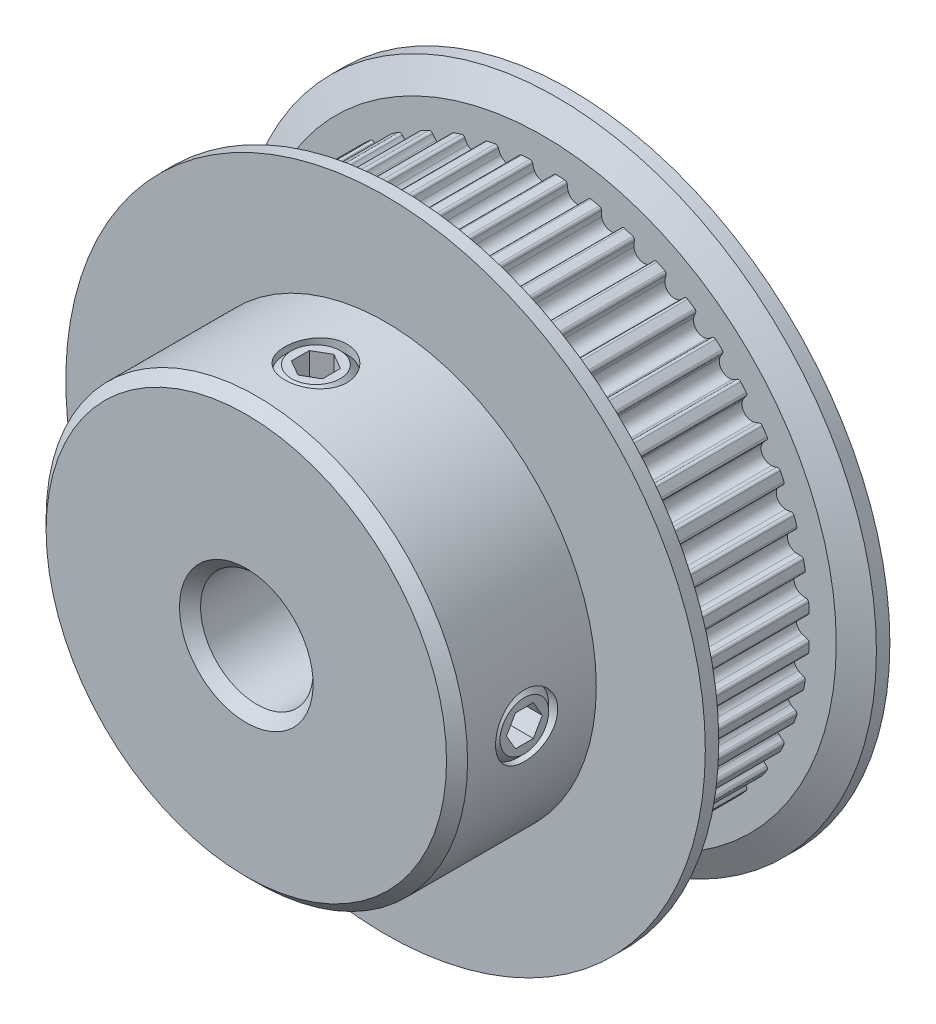
SolidWorks part; units mm, degrees
ref_plane "Front Plane" through (0, 0, 0) normal (0, 0, 1) x (1, 0, 0)
ref_plane "Top Plane" through (0, 0, 0) normal (0, 1, 0) x (1, 0, 0)
ref_plane "Right Plane" through (0, 0, 0) normal (1, 0, 0) x (0, 0, -1)
sketch "Sketch1" plane through (0, 0, 0) normal (0, 0, 1) x (1, 0, 0)
  line L1 (-1.8807, 14.274) -> (1.8807, 14.274) construction
  line L4 (0, 0) -> (0, 14.274) construction
  line L5 (0, 14.274) -> (0, 16.8906) construction
  line L6 (0, 15.278) -> (1.9957, 15.1471) construction
  line L7 (1.9957, 15.1471) -> (2.8688, 15.0321) construction
  line L8 (1.9957, 15.1471) -> (1.8807, 14.274) construction
  line L9 (-1.9957, 15.1471) -> (-1.8807, 14.274) construction
  line L10 (-1.9625, 14.8953) -> (-2.3761, 18.034)
  line L11 (-2.3761, 18.034) -> (2.3761, 18.034)
  line L12 (2.3761, 18.034) -> (1.9625, 14.8953)
  circle A0 centre (0, 0) radius 15.278 construction
  circle A1 centre (0, 0) radius 18.034 construction
  circle A2 centre (0, 0) radius 15.024 construction
  arc A3 (-0.4989, 14.5858) -> (0.4989, 14.5858) centre (0, 14.829) ccw
  arc A4 (-0.4989, 14.5858) -> (-0.5892, 14.8777) centre (0.4, 15.024) cw
  arc A5 (-1.9625, 14.8953) -> (-0.7451, 15.0055) centre (0, 0) cw
  arc A6 (-0.5892, 14.8777) -> (-0.7451, 15.0055) centre (-0.7376, 14.8557) ccw
  arc A7 (1.9625, 14.8953) -> (0.7451, 15.0055) centre (0, 0) ccw
  arc A8 (0.5892, 14.8777) -> (0.7451, 15.0055) centre (0.7376, 14.8557) cw
  arc A9 (0.4989, 14.5858) -> (0.5892, 14.8777) centre (-0.4, 15.024) ccw
  point P6 (0, 20.9083)
  point P11 (0, 15.278)
  point P13 (0, 18.034)
  point P14 (0, 15.024)
  dimension "D1" = 4.0177
  dimension "D2" = 1.6126
sketch "Sketch2" plane through (0, 0, 0) normal (1, 0, 0) x (0, 0, -1)
  line L0 (-9.1313, 3.175) -> (9.1313, 3.175)
  line L1 (-9.1313, 3.175) -> (-9.1313, 11.885)
  line L2 (-9.1313, 11.885) -> (-1.2787, 11.885)
  line L3 (-1.2787, 11.885) -> (-1.2787, 18.034)
  line L4 (-1.2787, 18.034) -> (0.2413, 18.034) construction
  line L5 (0.2413, 18.034) -> (0.2413, 15.024) construction
  line L6 (0.2413, 15.024) -> (7.6113, 15.024)
  line L7 (7.6113, 15.024) -> (7.6113, 18.034) construction
  line L8 (7.6113, 18.034) -> (9.1313, 18.034) construction
  line L9 (9.1313, 18.034) -> (9.1313, 3.175)
  line L10 (-9.1313, 0) -> (9.1313, 0) construction
  line L11 (8.3713, 18.034) -> (7.6113, 16.529)
  line L12 (0.2413, 16.529) -> (-0.5187, 18.034)
  line L13 (-1.2787, 18.034) -> (-0.5187, 18.034)
  line L14 (0.2413, 16.529) -> (0.2413, 15.024)
  line L15 (7.6113, 15.024) -> (7.6113, 16.529)
  line L16 (8.3713, 18.034) -> (9.1313, 18.034)
  arc A0 (0.2413, 16.529) -> (-0.5187, 18.034) centre (-1.6288, 16.529) ccw construction
  arc A1 (7.6113, 16.529) -> (8.3713, 18.034) centre (9.4814, 16.529) cw construction
  point P12 (0.2413, 16.529)
  point P14 (-0.5187, 18.034)
  point P20 (7.6113, 16.529)
  point P21 (8.3713, 18.034)
  point P25 (7.6113, 0)
  point P26 (0.2413, 0)
revolve "Revolve1" add sketch "Sketch2" angle 360 mid plane about L10
sketch "Sketch3" plane through (0, 0, 0) normal (0, 0, 1) x (1, 0, 0)
  line L6 (2.3761, 18.034) -> (-2.3761, 18.034)
  line L7 (1.9625, 14.8953) -> (2.3761, 18.034)
  line L8 (-2.3761, 18.034) -> (-1.9625, 14.8953)
  line L9 (2.3761, 18.034) -> (-2.3761, 18.034)
  line L10 (1.9625, 14.8953) -> (2.3761, 18.034)
  line L11 (-2.3761, 18.034) -> (-1.9625, 14.8953)
  arc A8 (1.9625, 14.8953) -> (0.7451, 15.0055) centre (0, 0) ccw
  arc A9 (0.7451, 15.0055) -> (0.5892, 14.8777) centre (0.7376, 14.8557) ccw
  arc A10 (0.4989, 14.5858) -> (0.5892, 14.8777) centre (-0.4, 15.024) ccw
  arc A11 (-0.4989, 14.5858) -> (0.4989, 14.5858) centre (0, 14.829) ccw
  arc A12 (-0.5892, 14.8777) -> (-0.4989, 14.5858) centre (0.4, 15.024) ccw
  arc A13 (-0.5892, 14.8777) -> (-0.7451, 15.0055) centre (-0.7376, 14.8557) ccw
  arc A14 (-0.7451, 15.0055) -> (-1.9625, 14.8953) centre (0, 0) ccw
  arc A15 (1.9625, 14.8953) -> (0.7451, 15.0055) centre (0, 0) ccw
  arc A16 (0.7451, 15.0055) -> (0.5892, 14.8777) centre (0.7376, 14.8557) ccw
  arc A17 (0.4989, 14.5858) -> (0.5892, 14.8777) centre (-0.4, 15.024) ccw
  arc A18 (-0.4989, 14.5858) -> (0.4989, 14.5858) centre (0, 14.829) ccw
  arc A19 (-0.5892, 14.8777) -> (-0.4989, 14.5858) centre (0.4, 15.024) ccw
  arc A20 (-0.5892, 14.8777) -> (-0.7451, 15.0055) centre (-0.7376, 14.8557) ccw
  arc A21 (-0.7451, 15.0055) -> (-1.9625, 14.8953) centre (0, 0) ccw
  dimension "D1" = 0
extrude "Cut-Extrude1" cut sketch "Sketch3" against normal up to vertex (7.6113 mm away) from vertex up to point (0, 15.024, -7.6113) starting at point (0, 15.024, -0.2413)
pattern_circular "CirPattern1" count 48 over 360 about axis through (0, 0, 9.1313) along (0, 0, 1) of "Cut-Extrude1"
sketch "Sketch4" plane through (0, 0, 0) normal (1, 0, 0) x (0, -1, 0)
  line L0 (0, -1.2787) -> (0, -9.1313) construction
  line L1 (-11.885, -1.2787) -> (11.885, -1.2787) construction
  line L2 (-11.885, -9.1313) -> (11.885, -9.1313) construction
  circle A0 centre (0, -5.205) radius 1.7526
extrude "Cut-Extrude2" cut sketch "Sketch4" along normal through all
ref_plane "Plane1" through (0, 0, 5.205) normal (0, 0, 1) x (1, 0, 0)
sketch "Sketch5" plane through (0, 0, 5.205) normal (0, 0, 1) x (1, 0, 0)
  line L0 (0, 0.1664) -> (0, 11.885) construction
  line L1 (3.175, -1.3716) -> (3.175, 0)
  line L2 (3.556, -1.7526) -> (11.3741, -1.7526)
  line L3 (3.175, 0) -> (11.885, 0) construction
  line L4 (3.175, 0) -> (11.7551, 0)
  line L5 (11.7551, 0) -> (11.7551, -1.3716)
  line L6 (3.556, -1.7526) -> (3.175, -1.3716)
  line L7 (11.7551, -1.3716) -> (11.3741, -1.7526)
  circle A0 centre (0, 0) radius 11.885 construction
  circle A1 centre (0, 0) radius 3.175 construction
  point P2 (3.175, -1.7526)
  point P11 (11.7551, -1.7526)
revolve "Revolve2" add sketch "Sketch5" angle 360 mid plane about L4
sketch "Sketch6" plane through (11.7551, 5.3841, 0) normal (-1, 0, 0) x (0, -1, 0)
  line L1 (5.3841, 6.2169) -> (4.5078, 5.7109)
  line L2 (4.5078, 5.7109) -> (4.5078, 4.6991)
  line L3 (4.5078, 4.6991) -> (5.3841, 4.1931)
  line L4 (5.3841, 4.1931) -> (6.2604, 4.6991)
  line L5 (6.2604, 4.6991) -> (6.2604, 5.7109)
  line L6 (6.2604, 5.7109) -> (5.3841, 6.2169)
  circle A0 centre (5.3841, 5.205) radius 0.8763 construction
  dimension "D1" = 1.7526
extrude "Cut-Extrude3" cut sketch "Sketch6" along normal blind 1.3144
pattern_circular "CirPattern2" count 2 over 90 about axis through (0, 0, 9.1313) along (0, 0, 1) of "Cut-Extrude2", "Revolve2", "Cut-Extrude3"
chamfer "Chamfer1" distance 0.5943 angle 45 2 edges at (3.175, 0, 9.1313) (11.885, 0, 9.1313)
ref_axis "Center Axis 1" through (0, 0, -9.1313) along (0, 0, 1)
ref_plane "Contact Plane 1" through (0, 0, 9.1313) normal (0, 0, 1) x (1, 0, 0)
ref_plane "Contact Plane 2" through (0, 0, -9.1313) normal (0, 0, -1) x (-1, 0, 0)
equation "\"D2@Sketch1\" = \"D1@Sketch1\"/2"
equation "\"D1@Sketch6\" = \"Set Screw@Sketch4\" / 2"
equation "\"D1@Cut-Extrude3\" = \"D1@Sketch6\"*.75"
equation "\"D1@Chamfer1\"=\"Hub Dia@Sketch2\"*.025"
